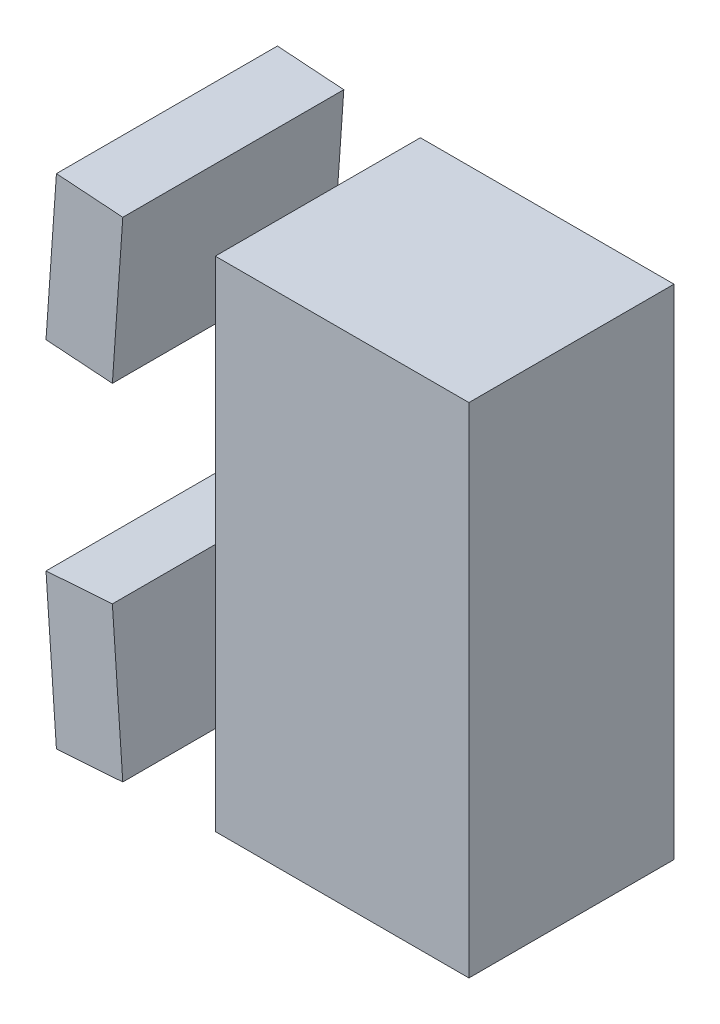
SolidWorks part; units mm, degrees
ref_plane "Front Plane" through (0, 0, 0) normal (0, 0, 1) x (1, 0, 0)
ref_plane "Top Plane" through (0, 0, 0) normal (0, 1, 0) x (1, 0, 0)
ref_plane "Right Plane" through (0, 0, 0) normal (1, 0, 0) x (0, 0, -1)
sketch "Sketch1" plane through (0, 0, 0) normal (0, 0, 1) x (1, 0, 0)
  line L0 (32.7383, 9.5052) -> (32.7383, -9.1865) construction
  line L1 (0, 0) -> (0.815, 11.6555) construction
  line L2 (0, 0) -> (-1531.3654, 0) construction
  line L3 (0.815, 11.6555) -> (1.8287, 26.1518)
  line L4 (1.8287, 26.1518) -> (11.3305, 25.4874)
  line L5 (11.3305, 25.4874) -> (10.8237, 18.2392)
  line L6 (10.6576, -15.8638) -> (1.1558, -16.5282) construction
  line L7 (10.9898, 20.6147) -> (10.6576, 15.8638) construction
  line L8 (10.9898, 20.6147) -> (1.488, 21.2791) construction
  line L9 (1.488, 21.2791) -> (1.1558, 16.5282) construction
  line L10 (10.6576, 15.8638) -> (1.1558, 16.5282) construction
  line L11 (1.488, -21.2791) -> (1.1558, -16.5282) construction
  line L12 (10.9898, -20.6147) -> (1.488, -21.2791) construction
  line L13 (10.9898, -20.6147) -> (10.6576, -15.8638) construction
  line L14 (0, 0) -> (0.815, -11.6555) construction
  line L15 (11.3305, -25.4874) -> (10.8237, -18.2392)
  line L16 (1.8287, -26.1518) -> (11.3305, -25.4874)
  line L17 (0.815, -11.6555) -> (1.8287, -26.1518)
  line L18 (41.4695, -1.5875) -> (21.1495, -1.5875)
  line L19 (41.4695, -1.5875) -> (41.4695, 1.5875)
  line L20 (41.4695, 1.5875) -> (21.1495, 1.5875)
  line L22 (37.5008, 9.5052) -> (37.5008, -9.1865) construction
  line L23 (32.7383, -9.1865) -> (37.5008, -9.1865) construction
  line L24 (32.7383, 9.5052) -> (37.5008, 9.5052) construction
  line L25 (20.6072, 5.0165) -> (41.4695, 5.0165)
  line L26 (41.4695, 5.0165) -> (41.4695, 8.1915)
  line L27 (41.4695, 8.1915) -> (19.5633, 8.1915)
  line L28 (28.7695, 9.5052) -> (41.4695, 9.5052) construction
  line L29 (41.4695, -8.1915) -> (19.5633, -8.1915)
  line L30 (41.4695, -5.0165) -> (41.4695, -8.1915)
  line L31 (20.6072, -5.0165) -> (41.4695, -5.0165)
  line L32 (28.7695, 9.5052) -> (28.7695, -9.1865) construction
  line L33 (28.7695, -9.1865) -> (41.4695, -9.1865) construction
  line L34 (41.4695, -9.1865) -> (41.4695, 9.5052) construction
  arc A0 (0.815, 11.6555) -> (0, 11.684) centre (0, 0) cw
  arc A1 (10.8237, 18.2392) -> (10.8237, -18.2392) centre (0, 0) cw
  arc A2 (1.4795, 21.1573) -> (0, 21.209) centre (0, 0) cw construction
  arc A3 (0.815, -11.6555) -> (0, 11.684) centre (0, 0) ccw
  point P4 (-25.5636, 4.1104)
  point P13 (1.3219, 18.9037)
  point P14 (41.4695, 0)
  point P17 (1.3219, 18.9037)
  point P24 (10.8237, 18.2392)
  point P42 (35.1195, 9.5052)
  dimension "D2" = 11.684
  dimension "D4" = 9.525
  dimension "D5" = 4.7625
  dimension "D1" = 94
  dimension "D6" = 3.175
  dimension "D7" = 4.7625
  dimension "D8" = 3.429
  dimension "D9" = 20.32
  dimension "D10" = 12.7
  dimension "D11" = 7.2658
  dimension "D3" = 9.525
extrude "Body" add sketch "Sketch1" along normal blind 19.05 contours A3 L17 L16 L15 A1 L5 L4 L3 A0 | L31 A1 L29 L30 | L20 A1 L18 L19 | L27 A1 L25 L26 region at (1.8819, 18.8645, 0) region at (30.7984, 6.6169, 0) region at (30.7984, -6.6169, 0) region at (31.3293, 0, 0)
hole_wizard "CBORE for #10 Binding Head Machine Screw1" positions "Sketch2" profile "Sketch3" counterbore size "#10" standard "ANSI Inch" end condition through all
sketch "Sketch2" plane through (9.5018, 0.6644, 0) normal (0.9976, 0.0698, 0) x (0.0698, -0.9976, 0)
  line L0 (18.9498, -19.05) -> (18.9498, 0) construction
  point P0 (18.9498, -9.525)
sketch "Sketch3" plane through (10.8237, -18.2392, 9.525) normal (0, 0, 1) x (-0.0698, 0.9976, 0)
  line L0 (0, 0) -> (0, 10.5362)
  line L1 (0, 10.5362) -> (2.5527, 10.5362)
  line L3 (2.5527, 10.5362) -> (2.5527, 3.1242)
  line L4 (2.5527, 3.1242) -> (5.9436, 3.1242)
  line L5 (5.9436, 3.1242) -> (5.9436, 0)
  line L7 (5.9436, 0) -> (0, 0)
  line L11 (0, -6.35) -> (0, 107.95) construction
  dimension "Thru Hole Dia." = 5.1054
  dimension "Thru Hole Depth" = 10.5362
  dimension "C'Bore Dia." = 11.8872
  dimension "C'Bore Depth" = 3.1242
sketch "Sketch4" plane through (6.3852, 0.4465, 0) normal (0.9976, 0.0698, 0) x (-0.0698, 0.9976, 0)
  circle A1 centre (-18.9498, 9.525) radius 5.9436
  circle A2 centre (-18.9498, 9.525) radius 5.9436
  dimension "D1" = 0
extrude "#10 Head clearance" cut sketch "Sketch4" along normal through all
sketch "Sketch5" plane through (9.5018, -0.6644, 0) normal (0.9976, -0.0698, 0) x (-0.0698, -0.9976, 0)
  line L0 (-18.9498, -19.05) -> (-18.9498, 0) construction
  line L1 (-23.9028, -6.6654) -> (-23.9028, -12.3846)
  line L2 (-23.9028, -12.3846) -> (-18.9498, -15.2442)
  line L3 (-18.9498, -15.2442) -> (-13.9968, -12.3846)
  line L4 (-13.9968, -12.3846) -> (-13.9968, -6.6654)
  line L5 (-13.9968, -6.6654) -> (-18.9498, -3.8058)
  line L6 (-18.9498, -3.8058) -> (-23.9028, -6.6654)
  circle A2 centre (-18.9498, -9.525) radius 4.953 construction
  point P0 (-23.4309, -5.9712)
  point P3 (0, 0)
  point P11 (0, 0)
  point P12 (-17.7856, -9.525)
  line M7 (-18.9498, -19.05) -> (-18.9498, 0)
  line M9 (-18.9498, -19.05) -> (-18.9498, 0)
  dimension "D1" = 9.906
extrude "#10 nut clearance" cut sketch "Sketch5" along direction (0.9976, -0.0698, 0) on the side against the normal blind 4.7625 and the other way through all contours L6 L1 L2 M9 M7 | L4 L5 L3 M9 M7 region at (10.9772, 20.4352, 9.525) region at (10.6701, 16.0433, 9.525)
fillet "Fillet2" radius 8.89 6 edges at (41.4695, -6.604, 0) (41.4695, 0, 0) (41.4695, 6.604, 0) (41.4695, 6.604, 19.05) (41.4695, 0, 19.05) (41.4695, -6.604, 19.05)
hole_wizard "#10 Clearance Hole1" positions "Sketch7" profile "Sketch8" hole size "#10" standard "ANSI Inch" end condition through all
sketch "Sketch7" plane through (0, -8.1915, 0) normal (0, -1, 0) x (-1, 0, 0)
  line L0 (-41.4695, -9.525) -> (-19.5633, -9.525) construction
  line L1 (-41.4695, -10.16) -> (-41.4695, -8.89) construction
  line L2 (-19.5633, -19.05) -> (-19.5633, 0) construction
  circle A0 centre (-31.9445, -9.525) radius 9.525 construction
  point P9 (-31.9445, -9.525)
  dimension "D1" = 19.05
sketch "Sketch8" plane through (31.9445, -8.1915, 9.525) normal (1, 0, 0) x (0, 0, -1)
  line L0 (0, 0) -> (0, 34.3433)
  line L1 (0, 34.3433) -> (2.5527, 34.3433)
  line L2 (2.5527, 34.3433) -> (2.5527, 0)
  line L5 (2.5527, 0) -> (0, 0)
  line L11 (0, -6.35) -> (0, 107.95) construction
  dimension "Thru Hole Dia." = 5.1054
  dimension "Thru Hole Depth" = 34.3433
fillet "Fillet3" radius 5.08 2 edges at (19.5633, 8.1915, 9.525) (19.5633, -8.1915, 9.525)
fillet "Fillet4" radius 2.54 10 edges at (10.8237, 18.2392, 1.9029) (10.8237, 18.2392, 17.1471) (10.8237, -18.2392, 1.7907) (10.8237, -18.2392, 17.2593) (11.3305, -25.4874, 9.525) (1.8287, -26.1518, 9.525) (1.8287, 26.1518, 9.525) (0.815, -11.6555, 9.525) (0.815, 11.6555, 9.525) (11.3305, 25.4874, 9.525)
hole_wizard "#10 Clearance Hole2" positions "Sketch12" profile "Sketch13" hole size "#10" standard "ANSI Inch" end condition through all
sketch "Sketch12" plane through (4.7509, -0.3322, 0) normal (0.9976, -0.0698, 0) x (0, 0, -1)
  point P0 (-9.525, 18.9498)
sketch "Sketch13" plane through (6.0728, 18.5715, 9.525) normal (0, 0, 1) x (0.0698, 0.9976, 0)
  line L0 (0, 0) -> (0, 5.6071)
  line L1 (0, 5.6071) -> (2.5527, 5.6071)
  line L2 (2.5527, 5.6071) -> (2.5527, 0)
  line L5 (2.5527, 0) -> (0, 0)
  line L11 (0, -6.35) -> (0, 107.95) construction
  dimension "Thru Hole Dia." = 5.1054
  dimension "Thru Hole Depth" = 5.6071
sketch "Sketch11" plane through (0, 0, 0) normal (-0.9976, -0.0698, 0) x (0, 0, 1)
  line L13 (-2.4358, -27.0353) -> (21.4858, -27.0353)
  line L14 (-2.4358, -27.0353) -> (-2.4358, -10.8644)
  line L15 (-2.4358, -10.8644) -> (21.4858, -10.8644)
  line L16 (21.4858, -27.0353) -> (21.4858, -10.8644)
  line L17 (-2.4358, -27.0353) -> (21.4858, -10.8644) construction
  line L18 (-2.4358, -10.8644) -> (21.4858, -27.0353) construction
  point P0 (9.525, -18.9498)
extrude "Infill box -mount" add sketch "Sketch11" against normal offset from surface (7.2008 mm away) 0.8 separate body up to face at (7.529, -15.9107, 9.525) offset beyond the face yes
mirror "Mirror3" about plane through (0, 0, 0) normal (0, 1, 0) of bodies 108
sketch "Sketch9" plane through (0, 0, 0) normal (0, 1, 0) x (1, 0, 0)
  line L7 (45.6703, -20.6231) -> (18.2187, -20.6231)
  line L8 (45.6703, -20.6231) -> (45.6703, 1.5731)
  line L9 (45.6703, 1.5731) -> (18.2187, 1.5731)
  line L10 (18.2187, -20.6231) -> (18.2187, 1.5731)
  line L11 (45.6703, -20.6231) -> (18.2187, 1.5731) construction
  line L12 (45.6703, 1.5731) -> (18.2187, -20.6231) construction
  point P6 (31.9445, -9.525)
  point P12 (18.2187, -20.6231)
extrude "Infill bounding box" add sketch "Sketch9" along normal through all and the other way through all separate body
delete or keep bodies "Infill delete main body" type delete bodies bodies 111
equation "\"D2@Sketch1\"= \"yagi_diam\" / 2 + \"tol\""
equation "\"yagi_diam\"= 0.88"
equation "\"tol\"= 0.02"
equation "\"D1@Sketch5\"=0.37+\"tol\""
equation "\"D8@Sketch1\"=0.125+0.010"
